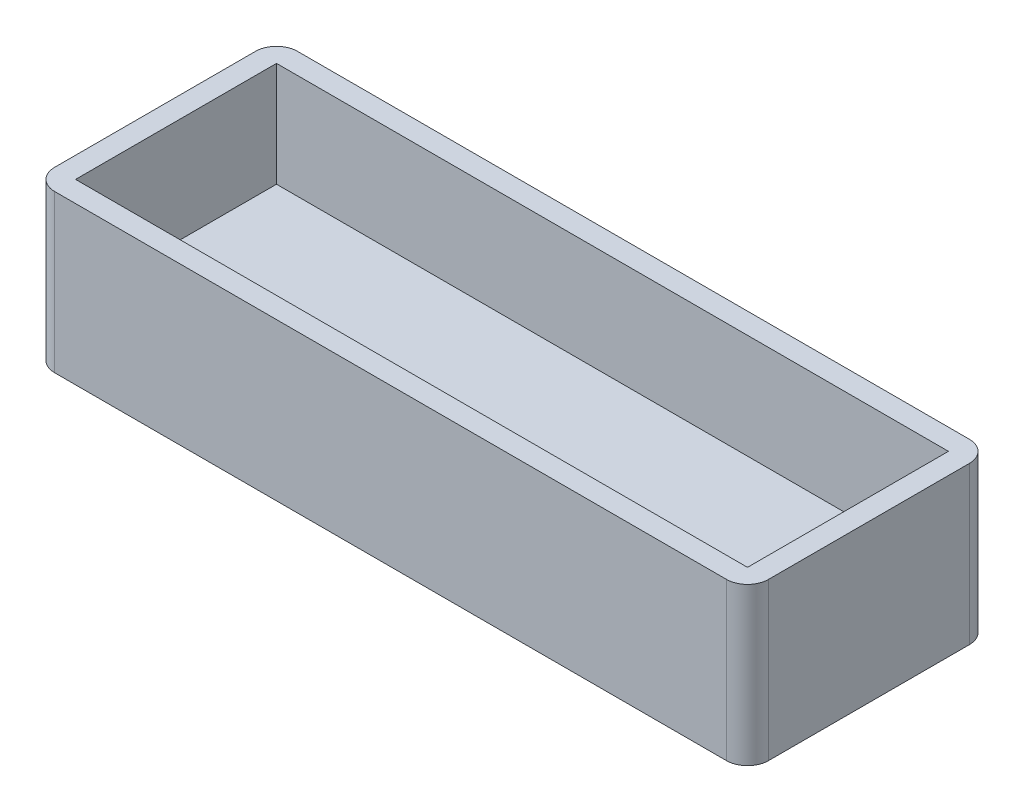
SolidWorks part; units mm, degrees
ref_plane "Front Plane" through (0, 0, 0) normal (0, 0, 1) x (1, 0, 0)
ref_plane "Top Plane" through (0, 0, 0) normal (0, 1, 0) x (1, 0, 0)
ref_plane "Right Plane" through (0, 0, 0) normal (1, 0, 0) x (0, 0, -1)
sketch "Sketch1" plane through (0, 0, 0) normal (0, 1, 0) x (1, 0, 0)
  line L0 (-2, -2) -> (-2, 21.2)
  line L1 (0, 0) -> (64.2, 0)
  line L2 (0, 0) -> (0, 19.2)
  line L3 (0, 19.2) -> (64.2, 19.2)
  line L4 (64.2, 0) -> (64.2, 19.2)
  line L5 (-2, 21.2) -> (66.2, 21.2)
  line L6 (66.2, -2) -> (66.2, 21.2)
  line L7 (-2, -2) -> (66.2, -2)
  dimension "D1" = 64.2
  dimension "D2" = 19.2
  dimension "D3" = 2
extrude "Boss-Extrude1" add sketch "Sketch1" along normal blind 10
extrude "Boss-Extrude2" add sketch "Sketch1<2>" against normal blind 5 contours L1 L4 L3 L2 | L0 L7 L6 L5 L4 L1 L2 L3 region at (-1.2796, 0, -9.6) region at (32.1, 0, -9.6)
sketch "Sketch1<2>" plane through (0, 0, 0) normal (0, 1, 0) x (1, 0, 0) same geometry as "Sketch1"
sketch "Sketch2" plane through (0, -5, 0) normal (0, -1, 0) x (1, 0, 0)
  line L0 (32.1, 2) -> (32.1, -21.2) construction
  line L1 (-2, 2) -> (66.2, 2) construction
  line L2 (-2, -21.2) -> (66.2, -21.2) construction
  line L3 (14.6, -9.6) -> (32.1, -9.6) construction
  circle A0 centre (14.6, -9.6) radius 2.5
  circle A1 centre (49.6, -9.6) radius 2.5
  dimension "D2" = 5
  dimension "D1" = 17.5
extrude "Boss-Extrude3" add sketch "Sketch2" along normal blind 5
fillet "Fillet1" radius 2 4 edges at (-2, 2.5, -21.2) (-2, 2.5, 2) (66.2, 2.5, -21.2) (66.2, 2.5, 2)
